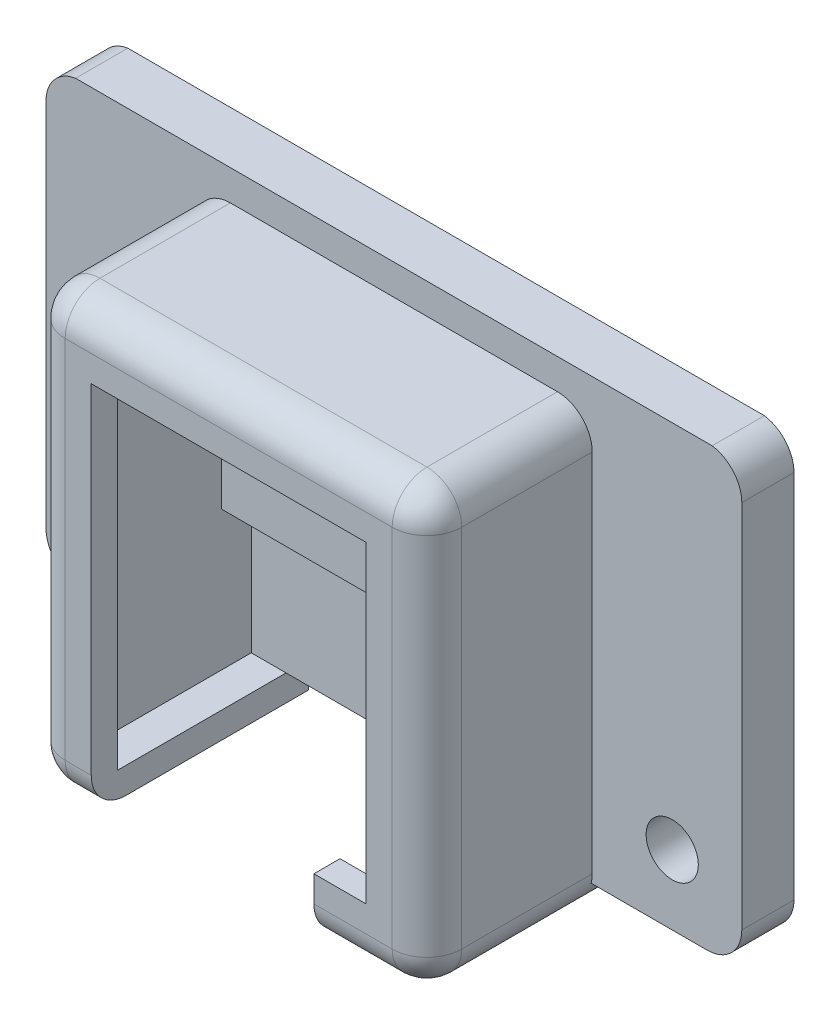
SolidWorks part; units mm, degrees
ref_plane "Alzado" through (0, 0, 0) normal (0, 0, 1) x (1, 0, 0)
ref_plane "Planta" through (0, 0, 0) normal (0, 1, 0) x (1, 0, 0)
ref_plane "Vista lateral" through (0, 0, 0) normal (1, 0, 0) x (0, 0, -1)
sketch "Croquis1" plane through (0, 0, 0) normal (0, 0, 1) x (1, 0, 0)
  line L2 (-75.3066, 17.9596) -> (-75.3066, -5.318)
  line L3 (-75.3066, -5.318) -> (-35.3066, -5.318)
  line L4 (-35.3066, 17.9596) -> (-35.3066, -5.318)
  line L6 (-55.3066, 22.682) -> (-35.3066, 22.682) construction
  line L8 (-73.6033, 19.9375) -> (-37.0099, 19.9375)
  circle A0 centre (-71.3066, -1.318) radius 1.5
  circle A1 centre (-39.3066, -1.318) radius 1.5
  arc A2 (-37.0099, 19.9375) -> (-35.3066, 17.9596) centre (-37.3066, 17.9596) cw
  arc A4 (-73.6033, 19.9375) -> (-75.3066, 17.9596) centre (-73.3066, 17.9596) ccw
  point P17 (-75.3066, 19.682)
  dimension "D3" = 2
  dimension "D4" = 32
  dimension "D5" = 3
  dimension "D6" = 3
  dimension "D1" = 4
  dimension "D2" = 3
  dimension "D7" = 4
  dimension "D8" = 4
extrude "Saliente-Extruir1" add sketch "Croquis1" along normal blind 3
sketch "Croquis2" plane through (0, 0, 3) normal (0, 0, 1) x (1, 0, 0)
  line L0 (-75.3066, -5.318) -> (-35.3066, -5.318) construction
  line L1 (-66.7066, -5.318) -> (-65.2066, -5.318)
  line L2 (-66.7066, -5.318) -> (-66.7066, 18.182)
  line L3 (-66.7066, 18.182) -> (-43.9066, 18.182)
  line L4 (-43.9066, -5.318) -> (-43.9066, 18.182)
  line L5 (-45.4066, -5.318) -> (-43.9066, -5.318)
  line L6 (-65.2066, 16.682) -> (-45.4066, 16.682)
  line L7 (-65.2066, 16.682) -> (-65.2066, -5.318)
  line L9 (-45.4066, 16.682) -> (-45.4066, -5.318)
  dimension "D1" = 22.8
  dimension "D3" = 23.5
  dimension "D4" = 1.5
  dimension "D5" = 1.5
  dimension "D6" = 1.5
extrude "Saliente-Extruir2" add sketch "Croquis2" along normal blind 8
sketch "Croquis3" plane through (0, -5.318, 0) normal (0, -1, 0) x (1, 0, 0)
  line L1 (-65.2066, 3) -> (-52.2066, 3)
  line L2 (-65.2066, 3) -> (-65.2066, 1.3)
  line L3 (-65.2066, 1.3) -> (-52.2066, 1.3)
  line L4 (-52.2066, 3) -> (-52.2066, 1.3)
  dimension "D1" = 13
  dimension "D2" = 1.7
extrude "Cortar-Extruir1" cut sketch "Croquis3" against normal blind 8
sketch "Croquis5" plane through (0, -5.318, 0) normal (0, -1, 0) x (1, 0, 0)
  line L0 (-75.3066, 0) -> (-35.3066, 0) construction
  line L1 (-66.7066, 11) -> (-63.2066, 11)
  line L2 (-66.7066, 11) -> (-66.7066, 0)
  line L3 (-66.7066, 0) -> (-63.2066, 0)
  line L4 (-63.2066, 11) -> (-63.2066, 0)
  line L5 (-45.4066, 11) -> (-45.4066, 3) construction
  line L6 (-43.9066, 11) -> (-50.4066, 11)
  line L7 (-43.9066, 11) -> (-43.9066, 0)
  line L8 (-43.9066, 0) -> (-50.4066, 0)
  line L9 (-50.4066, 11) -> (-50.4066, 0)
  line L10 (-65.2066, 11) -> (-65.2066, 1.3) construction
  dimension "D1" = 5
  dimension "D2" = 2
extrude "Saliente-Extruir3" add sketch "Croquis5" along normal blind 1.5
sketch "Croquis6" plane through (0, 0, 11) normal (0, 0, 1) x (1, 0, 0)
  line L0 (-63.2066, -5.318) -> (-63.2066, -6.818)
  line L1 (-63.2066, -6.818) -> (-66.7066, -6.818)
  line L2 (-66.7066, -6.818) -> (-66.7066, 18.182)
  line L3 (-66.7066, 18.182) -> (-43.9066, 18.182)
  line L4 (-43.9066, 18.182) -> (-43.9066, -6.818)
  line L5 (-43.9066, -6.818) -> (-50.4066, -6.818)
  line L6 (-50.4066, -6.818) -> (-50.4066, -3.318)
  line L7 (-50.4066, -3.318) -> (-47.4066, -3.318)
  line L8 (-47.4066, -3.318) -> (-47.4066, 14.682)
  line L9 (-47.4066, 14.682) -> (-63.2066, 14.682)
  line L10 (-63.2066, 14.682) -> (-63.2066, -5.318)
  dimension "D1" = 15.8
extrude "Saliente-Extruir4" add sketch "Croquis6" along normal blind 1.5
fillet "Redondeo1" radius 2 11 edges at (-43.9066, 18.182, 7.75) (-43.9066, -6.818, 6.25) (-66.7066, 18.182, 7.75) (-66.7066, -6.818, 6.25) (-64.9566, -6.818, 12.5) (-47.1566, -6.818, 12.5) (-43.9066, 5.682, 12.5) (-55.3066, 18.182, 12.5) (-66.7066, 5.682, 12.5) (-35.3066, -5.318, 1.5) (-75.3066, -5.318, 1.5)
